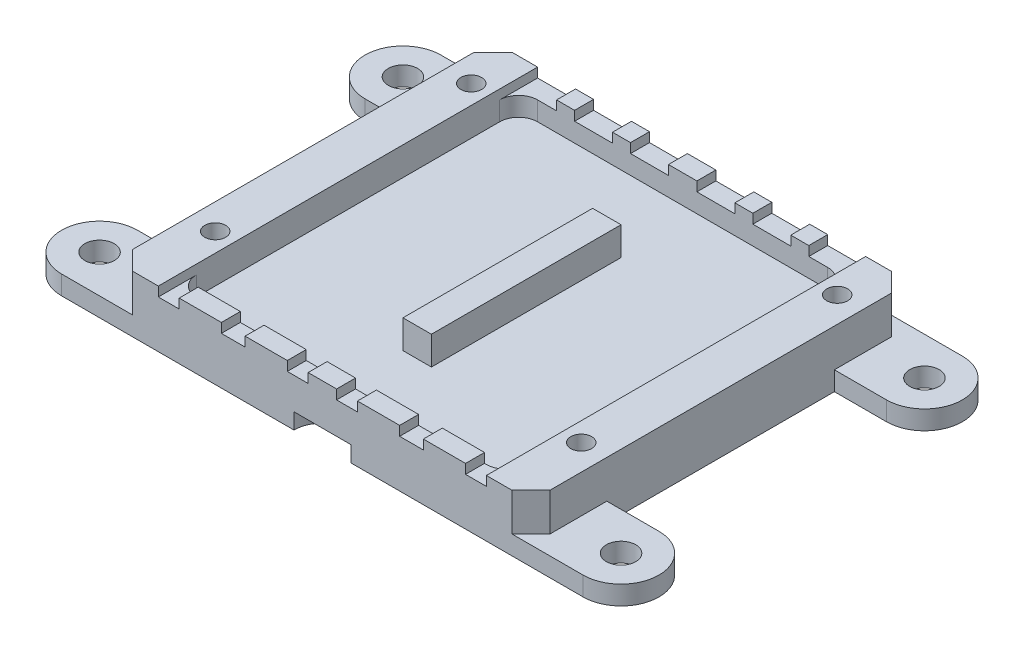
SolidWorks part; units mm, degrees
ref_plane "前视基准面" through (0, 0, 0) normal (0, 0, 1) x (1, 0, 0)
ref_plane "上视基准面" through (0, 0, 0) normal (0, 1, 0) x (1, 0, 0)
ref_plane "右视基准面" through (0, 0, 0) normal (1, 0, 0) x (0, 0, -1)
sketch "草图1" plane through (0, 0, 0) normal (0, 1, 0) x (1, 0, 0)
  line L0 (27.5, -20) -> (22, -20)
  line L2 (-22, -20) -> (-16, -20)
  line L3 (-16, 20) -> (16, 20)
  line L4 (-27.5, -12) -> (-22, -12)
  line L5 (-16, -20) -> (16, -20)
  line L6 (-22, 12) -> (-22, -12)
  line L7 (-22, 20) -> (22, -20) construction
  line L8 (-22, -20) -> (22, 20) construction
  line L9 (-22, 20) -> (-16, 20)
  line L10 (16, 20) -> (22, 20)
  line L11 (16, -20) -> (22, -20)
  line L12 (-27.5, 0) -> (-27.5, -16) construction
  line L13 (-27.5, -16) -> (27.5, -16) construction
  line L14 (27.5, -16) -> (27.5, 16) construction
  line L15 (27.5, 16) -> (-27.5, 16) construction
  line L16 (-27.5, 16) -> (-27.5, 0) construction
  line L17 (-22, -20) -> (-27.5, -20)
  line L18 (27.5, -12) -> (22, -12)
  line L19 (27.5, 12) -> (22, 12)
  line L20 (22, 20) -> (27.5, 20)
  line L21 (-22, 20) -> (-27.5, 20)
  line L22 (-27.5, 12) -> (-22, 12)
  line L23 (22, 12) -> (22, -12)
  circle A0 centre (-27.5, -16) radius 1.55
  circle A1 centre (-27.5, 16) radius 1.55
  circle A2 centre (27.5, 16) radius 1.55
  circle A3 centre (27.5, -16) radius 1.55
  arc A4 (27.5, -20) -> (27.5, -12) centre (27.5, -16) ccw
  arc A5 (-27.5, -12) -> (-27.5, -20) centre (-27.5, -16) ccw
  arc A6 (-27.5, 20) -> (-27.5, 12) centre (-27.5, 16) ccw
  arc A7 (27.5, 12) -> (27.5, 20) centre (27.5, 16) ccw
  point P5 (0, 0)
  point P31 (-22, 0)
  dimension "D1" = 40
  dimension "D2" = 44
extrude "凸台-拉伸1" add sketch "草图1" along normal blind 2
sketch "草图2" plane through (0, 2, 0) normal (0, 1, 0) x (1, 0, 0)
  line L1 (-27.5, -20) -> (27.5, -20) construction
  line L3 (27.5, 20) -> (-27.5, 20) construction
  line L4 (22, -20) -> (22, 20)
  line L5 (-22, -20) -> (22, -20)
  line L6 (-22, 20) -> (-22, -20)
  line L7 (22, 20) -> (-22, 20)
  line L8 (-22, 12) -> (-22, -12) construction
  line L9 (22, -12) -> (22, 12) construction
extrude "凸台-拉伸2" add sketch "草图2" along normal blind 4
sketch "草图3" plane through (0, 6, 0) normal (0, 1, 0) x (1, 0, 0)
  line L0 (-27.5525, 0) -> (27.6913, 0) construction
  line L1 (0, 25.4358) -> (0, -26.8932) construction
  line L2 (-1.5, 10) -> (-1.5, -10)
  line L3 (1.5, 10) -> (1.5, -10)
  line L15 (17.3, 18) -> (17.3, -18)
  line L16 (-17.3, 18) -> (-17.3, -18)
  line L20 (-22, -18) -> (22, -18)
  line L21 (-17.3, -18) -> (17.3, -18)
  line L22 (-17.3, 25.4358) -> (-17.3, -26.8932) construction
  line L23 (22, 18) -> (-22, 18)
  line L24 (17.3, 18) -> (-17.3, 18)
  line L25 (17.3, 25.4358) -> (17.3, -26.8932) construction
  line L26 (-1.5, -10) -> (1.5, -10)
  line L27 (-1.5, 10) -> (1.5, 10)
  line L28 (-27.5525, 10) -> (27.6913, 10) construction
  line L29 (-1.5, 25.4358) -> (-1.5, -26.8932) construction
  line L30 (-27.5525, -10) -> (27.6913, -10) construction
  line L31 (1.5, 25.4358) -> (1.5, -26.8932) construction
  dimension "D5" = 2
  dimension "D1" = 1.5
  dimension "D2" = 1.5
  dimension "D3" = 15.8
  dimension "D4" = 15.8
  dimension "D6" = 2
  dimension "D7" = 10
  dimension "D8" = 10
extrude "切除-拉伸1" cut sketch "草图3" against normal blind 3
sketch "草图4" plane through (0, 6, 0) normal (0, 1, 0) x (1, 0, 0)
  line L0 (-27.4831, 0) -> (27.2055, 0) construction
  line L1 (0, 25.5746) -> (0, -24.6723) construction
  line L2 (17.3, -18) -> (17.3, 18) construction
  line L3 (-17.3, 18) -> (-17.3, -18) construction
  line L4 (17.3, -20) -> (17.3, -18)
  line L5 (-17.3, 20) -> (-17.3, 18)
  line L6 (22, 20) -> (-22, 20) construction
  line L7 (-22, -20) -> (22, -20) construction
  line L8 (17.3, 20) -> (13.3, 20)
  line L9 (-17.3, -20) -> (-15.1, -20)
  line L10 (-13.3, 20) -> (-13.3, 18)
  line L11 (13.3, 18) -> (13.3, 20)
  line L12 (13.3, -18) -> (13.3, 20) construction
  line L13 (-13.3, 20) -> (-13.3, -18) construction
  line L14 (17.3, 18) -> (-17.3, 18) construction
  line L15 (17.3, 18) -> (13.3, 18)
  line L16 (-17.3, -18) -> (-17.3, -20)
  line L17 (-17.3, 20) -> (-17.3, -18) construction
  line L18 (17.3, 18) -> (17.3, 20)
  line L19 (17.3, -18) -> (17.3, 20) construction
  line L21 (-1.5, 10) -> (-1.5, -10) construction
  line L22 (1.5, -10) -> (1.5, 10) construction
  line L23 (-1.5, 20) -> (-1.5, 18)
  line L24 (5.5, 18) -> (5.5, 20)
  line L25 (-5.5, 20) -> (-5.5, 18)
  line L26 (1.5, -10) -> (1.5, 10) construction
  line L27 (-5.5, 20) -> (-5.5, -10) construction
  line L28 (-1.5, 20) -> (-5.5, 20)
  line L29 (-1.5, 18) -> (-5.5, 18)
  line L30 (1.5, 18) -> (1.5, 20)
  line L31 (-1.5, 10) -> (-1.5, -10) construction
  line L33 (-1.5, 20) -> (-1.5, -10) construction
  line L34 (1.5, -20) -> (3.7, -20)
  line L35 (1.5, -18) -> (3.7, -18)
  line L36 (-9.4, 25.5746) -> (-9.4, -24.6723) construction
  line L37 (9.4, 25.5746) -> (9.4, -24.6723) construction
  line L38 (7.4, 20) -> (7.4, 18)
  line L39 (11.4, 20) -> (11.4, 18)
  line L40 (-7.4, 20) -> (-7.4, 18)
  line L41 (-11.4, 20) -> (-11.4, 18)
  line L42 (-13.3, 20) -> (-17.3, 20)
  line L43 (-13.3, 18) -> (-17.3, 18)
  line L44 (-7.4, 20) -> (-11.4, 20)
  line L45 (-7.4, 18) -> (-11.4, 18)
  line L46 (5.5, 20) -> (1.5, 20)
  line L47 (5.5, 18) -> (1.5, 18)
  line L48 (11.4, 20) -> (7.4, 20)
  line L49 (11.4, 18) -> (7.4, 18)
  line L50 (-11.4, 25.5746) -> (-11.4, -24.6723) construction
  line L51 (-7.4, 25.5746) -> (-7.4, -24.6723) construction
  line L52 (7.4, 25.5746) -> (7.4, -24.6723) construction
  line L53 (11.4, 25.5746) -> (11.4, -24.6723) construction
  line L54 (-17.3, -18) -> (17.3, -18) construction
  line L55 (-17.3, -18) -> (-15.1, -18)
  line L56 (-15.1, -18) -> (-15.1, -20)
  line L57 (15.1, -20) -> (15.1, -18)
  line L58 (1.5, -18) -> (1.5, -20)
  line L59 (-1.5, -18) -> (-1.5, -20)
  line L60 (-3.7, -18) -> (-3.7, -20)
  line L61 (3.7, -18) -> (3.7, -20)
  line L62 (-10.65, -18) -> (-10.65, -20)
  line L63 (-8.15, -18) -> (-8.15, -20)
  line L64 (8.15, -18) -> (8.15, -20)
  line L65 (10.65, -18) -> (10.65, -20)
  line L66 (8.15, -18) -> (10.65, -18)
  line L67 (8.15, -20) -> (10.65, -20)
  line L68 (15.1, -18) -> (17.3, -18)
  line L69 (15.1, -20) -> (17.3, -20)
  line L70 (-3.7, -18) -> (-1.5, -18)
  line L71 (-3.7, -20) -> (-1.5, -20)
  line L72 (-10.65, -18) -> (-8.15, -18)
  line L73 (-10.65, -20) -> (-8.15, -20)
  line L74 (-10.65, 25.5746) -> (-10.65, -24.6723) construction
  line L75 (-8.15, 25.5746) -> (-8.15, -24.6723) construction
  line L76 (8.15, 25.5746) -> (8.15, -24.6723) construction
  line L77 (10.65, 25.5746) -> (10.65, -24.6723) construction
  dimension "D5" = 9.4
  dimension "D11" = 2.2
  dimension "D3" = 2
  dimension "D19" = 4
  dimension "D1" = 4
  dimension "D2" = 4
  dimension "D4" = 4
  dimension "D6" = 9.4
  dimension "D7" = 2
  dimension "D8" = 2
  dimension "D9" = 2
  dimension "D10" = 2
  dimension "D12" = 2.2
  dimension "D13" = 2.2
  dimension "D14" = 2.2
  dimension "D15" = 1.25
  dimension "D16" = 1.25
  dimension "D17" = 1.25
  dimension "D18" = 1.25
extrude "切除-拉伸2" cut sketch "草图4" against normal blind 1
fillet "圆角2" radius 2 4 edges at (17.3, 4, -18) (-17.3, 4, -18) (-17.3, 4, 18) (17.3, 4, 18)
sketch "草图5" plane through (0, 6, 0) normal (0, 1, 0) x (1, 0, 0)
  line L0 (-29.4032, 0) -> (28.1262, 0) construction
  line L1 (0, 28.1432) -> (0, -32.3448) construction
  line L8 (-22, 20) -> (-22, -20) construction
  line L9 (22, -20) -> (22, 20) construction
  circle A0 centre (19.3, 15) radius 1.1
  circle A1 centre (19.3, -12) radius 1.1
  circle A2 centre (-19.3, -12) radius 1.1
  circle A3 centre (-19.3, 15) radius 1.1
  dimension "D1" = 2.2
  dimension "D2" = 2.7
  dimension "D3" = 2.7
  dimension "D4" = 15
  dimension "D5" = 12
extrude "切除-拉伸3" cut sketch "草图5" against normal through all
sketch "草图6" plane through (0, 0, 0) normal (0, -1, 0) x (1, 0, 0)
  circle A0 centre (19.3, 12) radius 2
  circle A1 centre (-19.3, 12) radius 2
  circle A2 centre (-19.3, -15) radius 2
  circle A3 centre (19.3, -15) radius 2
  dimension "D1" = 4
extrude "切除-拉伸4" cut sketch "草图6" against normal blind 2.5
chamfer "Chamfer3" distance 2 angle 45 4 edges at (22, 4, 20) (-22, 4, 20) (-22, 4, -20) (22, 4, -20)
sketch "Sketch1" plane through (0, 0, 0) normal (0, -1, 0) x (1, 0, 0)
  line L0 (0, 0) -> (0, -20) construction
  line L1 (0, 0) -> (0, 20) construction
  line L2 (-27.5, 20) -> (27.5, 20) construction
  circle A0 centre (0, -20) radius 3
  circle A1 centre (0, 20) radius 3
extrude "Cut-Extrude1" cut sketch "Sketch1" against normal blind 1.67
